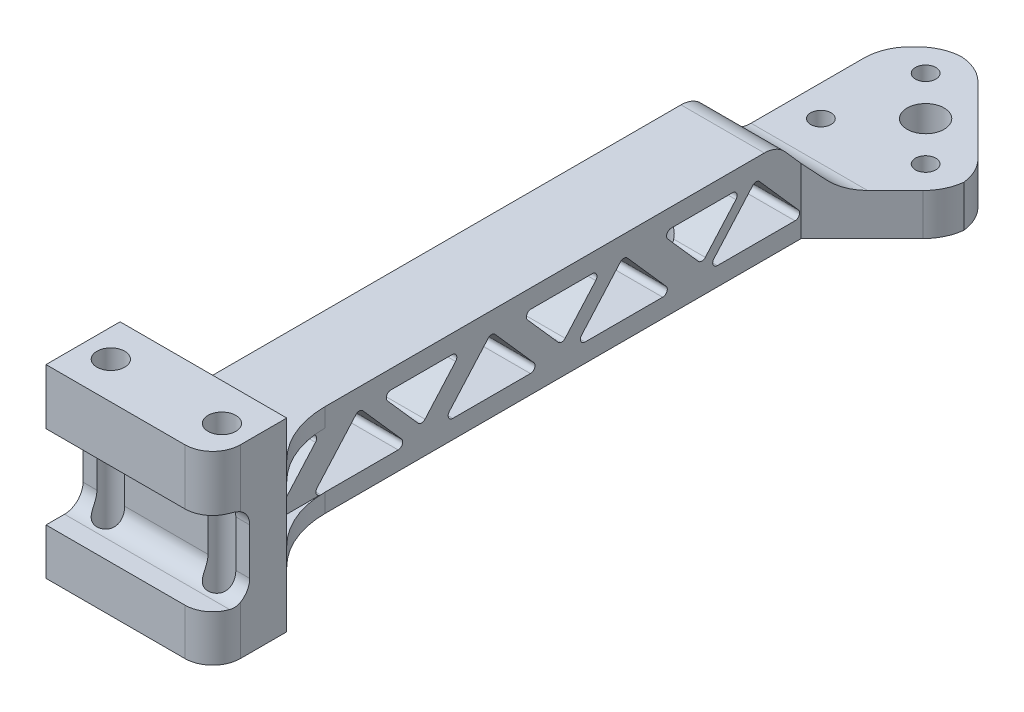
SolidWorks part; units mm, degrees
ref_plane "Front Plane" through (0, 0, 0) normal (0, 0, 1) x (1, 0, 0)
ref_plane "Top Plane" through (0, 0, 0) normal (0, 1, 0) x (1, 0, 0)
ref_plane "Right Plane" through (0, 0, 0) normal (1, 0, 0) x (0, 0, -1)
sketch "Sketch2" plane through (0, 0, 0) normal (0, 1, 0) x (1, 0, 0)
  line L0 (0, 54.2734) -> (0, -0.6821)
  line L1 (0, -0.6821) -> (15, -0.6821)
  line L2 (18, 2.3179) -> (18, 7.3179)
  line L3 (18, 7.3179) -> (11.9289, 13.389)
  line L4 (9, 20.46) -> (9, 71.8829)
  line L5 (9, 71.8829) -> (9, 85.3179) construction
  line L6 (3, 3.3179) -> (15, 3.3179) construction
  line L7 (0, 54.2734) -> (0, 89.7529)
  line L8 (0, 89.7529) -> (3.3076, 93.0605)
  line L9 (3.3076, 93.0605) -> (6.9142, 93.0605)
  line L10 (6.9142, 93.0605) -> (17.0459, 82.9288)
  line L11 (17.0459, 82.9288) -> (17.0459, 79.9288)
  line L12 (17.0459, 79.9288) -> (9, 71.8829)
  line L13 (9, 85.3179) -> (13.2426, 81.0752) construction
  line L14 (3.3431, 79.661) -> (9, 85.3179) construction
  line L15 (9, 85.3179) -> (4.7574, 89.5605) construction
  circle A0 centre (9, 85.3179) radius 6 construction
  circle A1 centre (9, 85.3179) radius 8 construction
  circle A2 centre (3, 3.3179) radius 1.5
  circle A3 centre (15, 3.3179) radius 1.5
  arc A4 (18, 2.3179) -> (15, -0.6821) centre (15, 2.3179) cw
  circle A5 centre (13.2426, 81.0752) radius 1.1
  circle A6 centre (3.3431, 79.661) radius 1.1
  circle A7 centre (4.7574, 89.5605) radius 1.1
  circle A8 centre (9, 85.3179) radius 2
  arc A9 (11.9289, 13.389) -> (9, 20.46) centre (19, 20.46) cw
  point P16 (18, 4.8179)
  point P19 (18, -0.6821)
  point P30 (17, 82.9747)
  dimension "D1" = 18
  dimension "D3" = 12
  dimension "D5" = 4
  dimension "D6" = 3
  dimension "D9" = 3
  dimension "D10" = 3
  dimension "D12" = 12
  dimension "D13" = 16
  dimension "D14" = 45
  dimension "D18" = 2.2
  dimension "D19" = 4
  dimension "D22" = 3.5
  dimension "D24" = 10
  dimension "D2" = 8
  dimension "D4" = 3
  dimension "D7" = 45
  dimension "D8" = 9
  dimension "D11" = 82
  dimension "D15" = 90
  dimension "D16" = 4
  dimension "D17" = 3.5
  dimension "D20" = 3.5
  dimension "D21" = 45
  dimension "D23" = 3
extrude "Boss-Extrude3" add sketch "Sketch2" along normal blind 10
sketch "Sketch3" plane through (0, 0, 0) normal (-1, 0, 0) x (0, 0, 1)
  line L0 (-93.0605, 8) -> (3.5707, 8) construction
  line L1 (-93.0605, 10) -> (-93.0605, 0) construction
  line L2 (3.5707, 8) -> (3.5707, 7) construction
  line L3 (3.5707, 7) -> (-94.6629, 7) construction
  line L4 (-94.6629, 7) -> (-94.6629, 5) construction
  line L5 (-94.6629, 5) -> (3.5707, 5) construction
  line L6 (3.5707, 5) -> (3.5707, 4.4818) construction
  line L7 (3.5707, 4.4818) -> (-94.6629, 4.4818) construction
  line L8 (-94.6629, 4.4818) -> (-94.6629, 3) construction
  line L9 (-94.6629, 3) -> (3.5707, 3) construction
  line L10 (3.5707, 3) -> (3.5707, 2) construction
  line L11 (3.5707, 2) -> (-94.6629, 2) construction
  line L12 (-89.7529, 10) -> (0.6821, 10) construction
  line L13 (-89.7529, 0) -> (0.6821, 0) construction
  line L14 (-7.3179, 8) -> (-7.3179, 2)
  line L15 (-7.3179, 2) -> (-12.6179, 2)
  line L16 (-12.6179, 2) -> (-7.3179, 8)
  line L17 (-11.3207, 8) -> (-15.7374, 3)
  line L18 (-15.7374, 3) -> (-20.154, 8)
  line L19 (-20.154, 8) -> (-11.3207, 8)
  line L20 (-18.8568, 2) -> (-24.1568, 8)
  line L21 (-24.1568, 8) -> (-29.4568, 2)
  line L22 (-29.4568, 2) -> (-18.8568, 2)
  line L23 (-26.4577, 8) -> (-30.8744, 3)
  line L24 (-30.8744, 3) -> (-35.2911, 8)
  line L25 (-35.2911, 8) -> (-26.4577, 8)
  line L26 (-41.5948, 8) -> (-46.0114, 3)
  line L27 (-46.0114, 3) -> (-50.4281, 8)
  line L28 (-50.4281, 8) -> (-41.5948, 8)
  line L29 (-56.7318, 8) -> (-61.1485, 3)
  line L30 (-61.1485, 3) -> (-65.5651, 8)
  line L31 (-65.5651, 8) -> (-56.7318, 8)
  line L32 (-43.7429, 2) -> (-33.1429, 2)
  line L33 (-33.1429, 2) -> (-38.4429, 8)
  line L34 (-38.4429, 8) -> (-43.7429, 2)
  line L35 (-58.029, 2) -> (-47.429, 2)
  line L36 (-47.429, 2) -> (-52.729, 8)
  line L37 (-52.729, 8) -> (-58.029, 2)
  line L38 (-72.3151, 2) -> (-61.7151, 2)
  line L39 (-61.7151, 2) -> (-67.0151, 8)
  line L40 (-67.0151, 8) -> (-72.3151, 2)
  line L41 (-76.3179, 2) -> (-71.0179, 8)
  line L42 (-71.0179, 8) -> (-76.3179, 8)
  line L43 (-76.3179, 8) -> (-76.3179, 2)
  line L44 (0.6821, 10) -> (0.6821, 0) construction
  point P51 (-73.6395, 2)
  point P52 (-72.3151, 2)
  point P53 (-61.1485, 3)
  point P54 (-60.0967, 3)
  point P55 (-61.7151, 2)
  point P56 (-62.5823, 2)
  point P57 (-32.6079, 2)
  point P58 (-54.3942, 8)
  point P59 (-35.776, 8)
  point P60 (-74.1822, 2)
  point P61 (-18.8568, 2)
  point P62 (-18.8568, 2)
  dimension "D1" = 2
  dimension "D2" = 2
  dimension "D3" = 1
  dimension "D4" = 1
  dimension "D5" = 2
  dimension "D6" = 2
  dimension "D7" = 5.3
  dimension "D8" = 3
  dimension "D9" = 3
  dimension "D12" = 8
  dimension "D13" = 77
  dimension "D14" = 3
  dimension "D15" = 3
  dimension "D10" = 4
  dimension "D11" = 4
extrude "Cut-Extrude1" cut sketch "Sketch3" against normal through all
sketch "Sketch5" plane through (9, 0, 0) normal (1, 0, 0) x (0, 0, -1)
  line L1 (7.3179, 8) -> (20.46, 8)
  line L2 (7.3179, 8) -> (7.3179, 2)
  line L3 (7.3179, 2) -> (20.46, 2)
  line L4 (20.46, 8) -> (20.46, 2)
  point P5 (0, 0)
  point P6 (20.46, 2)
extrude "Cut-Extrude3" cut sketch "Sketch5" along normal blind 30
fillet "Fillet4" radius 0.5 3 edges at (4.5, 8, -20.154) (4.5, 8, -11.3207) (4.5, 3, -15.7374)
fillet "Fillet6" radius 0.5 1 edges at (4.5, 2, -12.6179)
fillet "Fillet7" radius 0.5 1 edges at (9, 2, -7.3179)
fillet "Fillet8" radius 0.5 24 edges at (6.7175, 8, -76.3179) (6.7175, 2, -76.3179) (4.5, 8, -71.0179) (4.7161, 2, -72.3151) (4.5, 8, -67.0151) (4.5, 2, -61.7151) (4.5, 3, -61.1485) (4.5, 8, -65.5651) (4.5, 8, -56.7318) (4.5, 2, -58.029) (4.5, 8, -52.729) (4.5, 2, -47.429) (4.5, 3, -46.0114) (4.5, 8, -41.5948) (4.5, 8, -50.4281) (4.5, 2, -43.7429) (4.5, 2, -33.1429) (4.5, 8, -38.4429) (4.5, 8, -35.2911) (4.5, 8, -26.4577) (4.5, 3, -30.8744) (4.5, 2, -29.4568) (4.5, 8, -24.1568) (4.5, 2, -18.8568)
fillet "Fillet9" radius 0.5 1 edges at (4.5, 8, -7.3179) tangent propagation no
sketch "Sketch6" plane through (0, 10, 0) normal (0, 1, 0) x (1, 0, 0)
  line L0 (18, 7.3179) -> (0, 7.3179)
  line L1 (0, 89.7529) -> (0, -0.6821) construction
  line L2 (0, 7.3179) -> (0, -0.6821)
  line L3 (0, -0.6821) -> (15, -0.6821)
  line L4 (18, 2.3179) -> (18, 7.3179) construction
  line L5 (18, 2.3179) -> (18, 7.3179)
  arc A0 (15, -0.6821) -> (18, 2.3179) centre (15, 2.3179) ccw construction
  arc A1 (15, -0.6821) -> (18, 2.3179) centre (15, 2.3179) ccw
  circle A2 centre (3, 3.3179) radius 1.5 construction
  circle A3 centre (3, 3.3179) radius 1.5
  circle A5 centre (15, 3.3179) radius 1.5 construction
  circle A6 centre (15, 3.3179) radius 1.5
extrude "Boss-Extrude5" add sketch "Sketch6" along normal blind 10
sketch "Sketch7" plane through (0, 0, 0) normal (-1, 0, 0) x (0, 0, 1)
  line L0 (0.6821, 20) -> (0.6821, 0) construction
  line L1 (0.6821, 14) -> (-3.3179, 14)
  line L2 (0.6821, 14) -> (0.6821, 5)
  line L3 (0.6821, 5) -> (-3.3179, 5)
  line L4 (-3.3179, 14) -> (-3.3179, 5)
  line L5 (-89.7529, 0) -> (0.6821, 0) construction
  line L6 (-7.3179, 20) -> (0.6821, 20) construction
  dimension "D1" = 5
  dimension "D2" = 6
  dimension "D3" = 4
extrude "Cut-Extrude4" cut sketch "Sketch7" against normal through all
sketch "Sketch8" plane through (0, 0, 0) normal (-1, 0, 0) x (0, 0, 1)
  line L0 (-7.3179, 20) -> (-7.3179, 10)
  line L1 (-7.3179, 10) -> (-17.3179, 10)
  line L2 (-89.7529, 10) -> (-7.3179, 10) construction
  line L3 (-17.3179, 10) -> (-7.3179, 20)
  dimension "D1" = 45
extrude "Boss-Extrude6" add sketch "Sketch8" against normal blind 10
sketch "Sketch9" plane through (0, 0, 0) normal (-1, 0, 0) x (0, 0, 1)
  line L3 (-75.4431, 2.9903) -> (-71.7519, 7.169)
  line L4 (-76.3179, 7.5) -> (-76.3179, 3.3213)
  line L5 (-72.1267, 8) -> (-75.8179, 8)
  line L6 (-75.4431, 2.9903) -> (-71.7519, 7.169)
  line L7 (-76.3179, 7.5) -> (-76.3179, 3.3213)
  line L8 (-72.1267, 8) -> (-75.8179, 8)
  arc A3 (-76.3179, 3.3213) -> (-75.4431, 2.9903) centre (-75.8179, 3.3213) ccw
  arc A4 (-75.8179, 8) -> (-76.3179, 7.5) centre (-75.8179, 7.5) ccw
  arc A5 (-71.7519, 7.169) -> (-72.1267, 8) centre (-72.1267, 7.5) ccw
  arc A6 (-76.3179, 3.3213) -> (-75.4431, 2.9903) centre (-75.8179, 3.3213) ccw
  arc A7 (-75.8179, 8) -> (-76.3179, 7.5) centre (-75.8179, 7.5) ccw
  arc A8 (-71.7519, 7.169) -> (-72.1267, 8) centre (-72.1267, 7.5) ccw
  dimension "D1" = 0
extrude "Boss-Extrude7" add sketch "Sketch9" against normal up to surface (12.5603 mm away) up to face at (11.9923, 5.8714, -74.8751)
sketch "Sketch10" plane through (0, 0, 0) normal (-1, 0, 0) x (0, 0, 1)
  line L0 (-69.2512, 10) -> (-74.1095, 4.5)
  line L1 (-89.7529, 10) -> (-17.3179, 10) construction
  line L2 (-74.1095, 4.5) -> (-96.2776, 4.5)
  line L3 (-96.2776, 4.5) -> (-96.2776, 10)
  line L4 (-96.2776, 10) -> (-69.2512, 10)
  line L5 (-67.3898, 7.5758) -> (-71.581, 2.831) construction
  line L6 (-89.7529, 0) -> (0.6821, 0) construction
  dimension "D1" = 3
  dimension "D2" = 4.5
extrude "Cut-Extrude8" cut sketch "Sketch10" against normal through all
fillet "Fillet12" radius 2 2 edges at (9, 5, -3.3179) (9, 14, -3.3179)
chamfer "Chamfer1" distance 7 angle 50 1 edges at (10, 15, -12.3179) first distance on face at (10, 12.5, -12.0137)
fillet "Fillet13" radius 2 3 edges at (5.8289, 10, -12.3681) (5.8289, 15.0503, -7.3179) (14, 10, -7.3179)
fillet "Fillet14" radius 3 2 edges at (5.6133, 4.5, -74.1095) (4.5, 10, -69.2512)
fillet "Fillet15" radius 5 5 edges at (0, 2.25, -89.7529) (17.0459, 2.25, -79.9288) (17.0459, 2.25, -82.9288) (6.9142, 2.25, -93.0605) (3.3076, 2.25, -93.0605)
sketch "Sketch11" plane through (0, 0, 0) normal (0, -1, 0) x (1, 0, 0)
  line L0 (0, -87.6818) -> (0, 0.6821) construction
  circle A0 centre (4.5, -60.9033) radius 1.25
  dimension "D1" = 2.5
  dimension "D2" = 4.5
  dimension "D3" = 32.15
extrude "Cut-Extrude9" cut sketch "Sketch11" against normal blind 6
